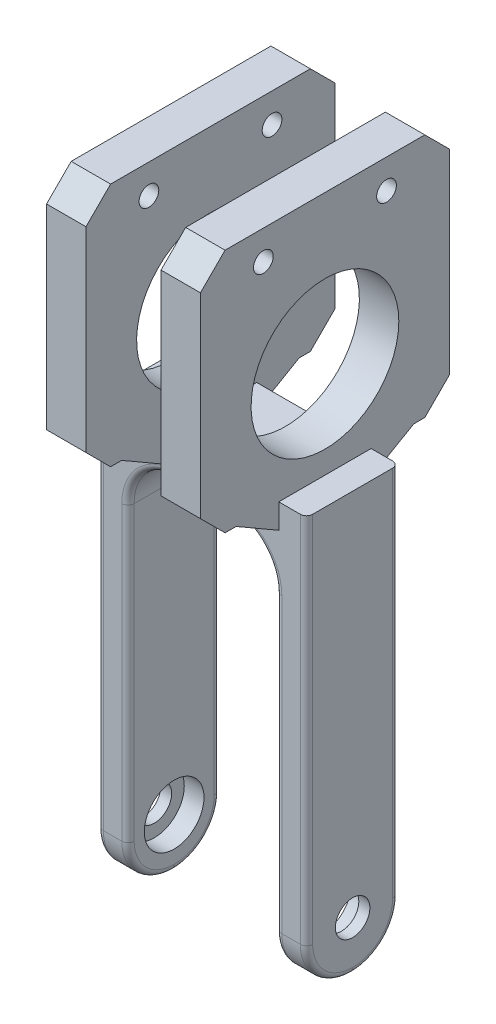
SolidWorks part; units mm, degrees
ref_plane "前视基准面" through (0, 0, 0) normal (0, 0, 1) x (1, 0, 0)
ref_plane "上视基准面" through (0, 0, 0) normal (0, 1, 0) x (1, 0, 0)
ref_plane "右视基准面" through (0, 0, 0) normal (1, 0, 0) x (0, 0, -1)
sketch "草图1" plane through (0, 0, 0) normal (0, 1, 0) x (1, 0, 0)
  line L1 (17, 7.5) -> (-17, 7.5)
  line L2 (17, 7.5) -> (17, -7.5)
  line L3 (17, -7.5) -> (-17, -7.5)
  line L4 (-17, 7.5) -> (-17, -7.5)
  line L5 (17, 7.5) -> (-17, -7.5) construction
  line L6 (17, -7.5) -> (-17, 7.5) construction
  point P0 (0, 0)
extrude "凸台-拉伸1" add sketch "草图1" against normal blind 68
sketch "草图3" plane through (0, 0, 7.5) normal (0, 0, 1) x (1, 0, 0)
  line L0 (-17, -68) -> (17, -68) construction
  line L1 (-12, -68) -> (12, -68)
  line L2 (-12, -68) -> (-12, -5)
  line L3 (-12, -5) -> (12, -5)
  line L4 (12, -68) -> (12, -5)
extrude "切除-拉伸1" cut sketch "草图3" against normal through all
fillet "圆角1" radius 8 2 edges at (12, -5, 0) (-12, -5, 0)
fillet "圆角3" radius 7.5 4 edges at (14.5, -68, -7.5) (14.5, -68, 7.5) (-14.5, -68, -7.5) (-14.5, -68, 7.5)
fillet "圆角2" radius 1 22 edges at (-17, -30.25, -7.5) (17, -30.25, -7.5) (17, -30.25, 7.5) (-17, -30.25, 7.5) (-9.6569, -7.3431, 7.5) (0, -5, 7.5) (9.6569, -7.3431, 7.5) (12, -36.75, 7.5) (12, -36.75, -7.5) (9.6569, -7.3431, -7.5) (0, -5, -7.5) (-9.6569, -7.3431, -7.5) (-12, -36.75, -7.5) (-12, -36.75, 7.5) (12, -65.8033, 5.3033) (12, -65.8033, -5.3033) (-12, -65.8033, -5.3033) (-12, -65.8033, 5.3033) (-17, -65.8033, 5.3033) (-17, -65.8033, -5.3033) (17, -65.8033, -5.3033) (17, -65.8033, 5.3033)
sketch "草图4" plane through (17, 0, 0) normal (1, 0, 0) x (0, 0, -1)
  circle A0 centre (0, -60) radius 2.8
extrude "切除-拉伸2" cut sketch "草图4" against normal through all
sketch "草图6" plane through (12, 0, 0) normal (1, 0, 0) x (0, 0, -1)
  circle A0 centre (0, -60) radius 4.85
extrude "切除-拉伸4" cut sketch "草图6" along normal blind 3.2
mirror "镜向1" about plane through (0, 0, 0) normal (1, 0, 0) of "切除-拉伸4"
sketch "草图7" plane through (0, 0, 0) normal (1, 0, 0) x (0, 0, -1)
  line L1 (-20.2247, 0) -> (20.2247, 0)
  line L2 (-20.2247, 0) -> (-20.2247, 39.7702)
  line L3 (-20.2247, 39.7702) -> (20.2247, 39.7702)
  line L4 (20.2247, 0) -> (20.2247, 39.7702)
  circle A0 centre (0, 15.6509) radius 12
  circle A1 centre (-10, 35) radius 1.6
  circle A2 centre (10, 35) radius 1.6
  point P4 (0, 0)
extrude "凸台-拉伸2" add sketch "草图7" along normal mid plane 25
sketch "草图8" plane through (0, 0, 20.2247) normal (0, 0, 1) x (1, 0, 0)
  line L0 (-12.5, 0) -> (12.5, 0) construction
  line L1 (-6.0956, 39.7702) -> (6.0956, 39.7702)
  line L2 (-6.0956, 39.7702) -> (-6.0956, 0)
  line L3 (-6.0956, 0) -> (6.0956, 0)
  line L4 (6.0956, 39.7702) -> (6.0956, 0)
  line L5 (-6.0956, 39.7702) -> (6.0956, 0) construction
  line L6 (-6.0956, 0) -> (6.0956, 39.7702) construction
  line L8 (12.5, 39.7702) -> (-12.5, 39.7702) construction
  point P0 (0, 19.8851)
extrude "切除-拉伸5" cut sketch "草图8" against normal through all
chamfer "倒角1" distance 4 angle 60 4 edges at (-9.2978, 0, 7.5) (9.2978, 0, 7.5) (9.2978, 0, -7.5) (-9.2978, 0, -7.5) first distance on face at (0, -19.448, 7.5) first distance on face at (0, -19.448, -7.5)
chamfer "倒角2" distance 4 angle 45 8 edges at (9.2978, 0, -20.2247) (-9.2978, 0, -20.2247) (-9.2978, 39.7702, -20.2247) (9.2978, 39.7702, -20.2247) (9.2978, 0, 20.2247) (-9.2978, 0, 20.2247) (9.2978, 39.7702, 20.2247) (-9.2978, 39.7702, 20.2247)
